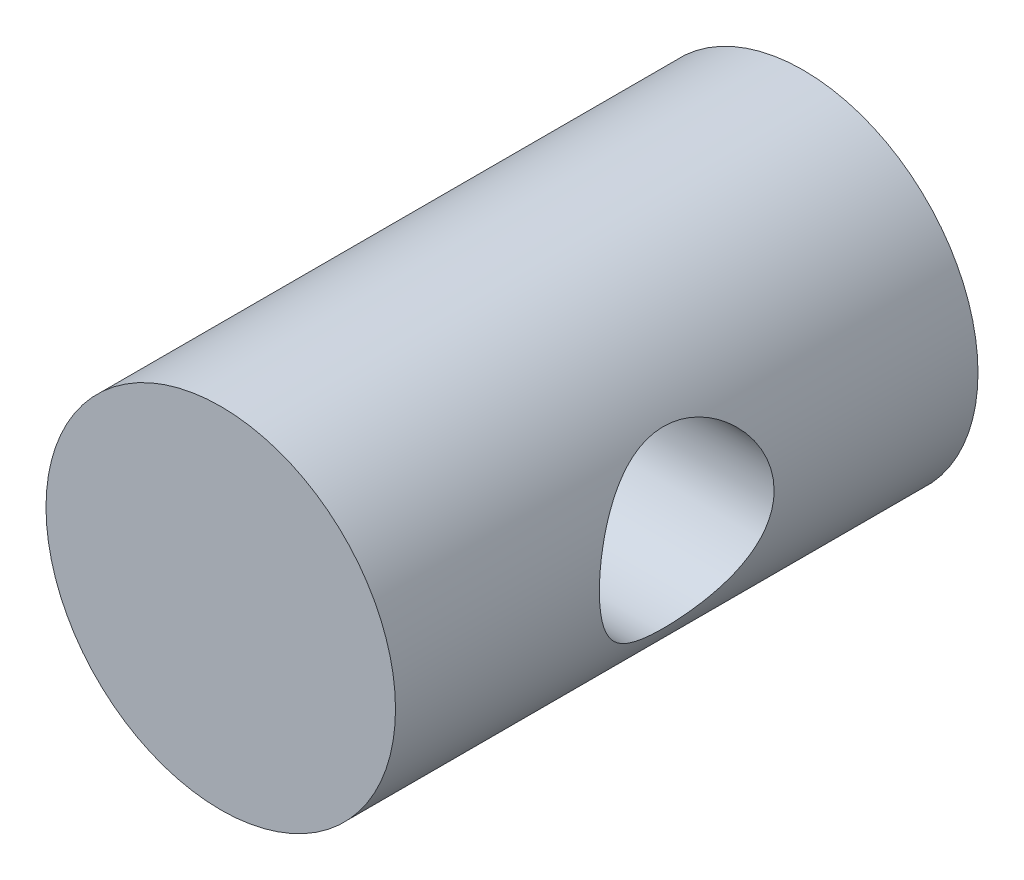
SolidWorks part; units mm, degrees
ref_plane "Front Plane" through (0, 0, 0) normal (0, 0, 1) x (1, 0, 0)
ref_plane "Top Plane" through (0, 0, 0) normal (0, 1, 0) x (1, 0, 0)
ref_plane "Right Plane" through (0, 0, 0) normal (1, 0, 0) x (0, 0, -1)
sketch "Sketch1" plane through (0, 0, 0) normal (0, 0, 1) x (1, 0, 0)
  circle A0 centre (0, 0) radius 3
extrude "Boss-Extrude1" add sketch "Sketch1" along normal blind 10
sketch "Sketch2" plane through (0, 0, 0) normal (1, 0, 0) x (0, 0, -1)
  circle A0 centre (-5, 0) radius 1.5
extrude "Cut-Extrude1" cut sketch "Sketch2" against normal blind 10 and the other way blind 10
